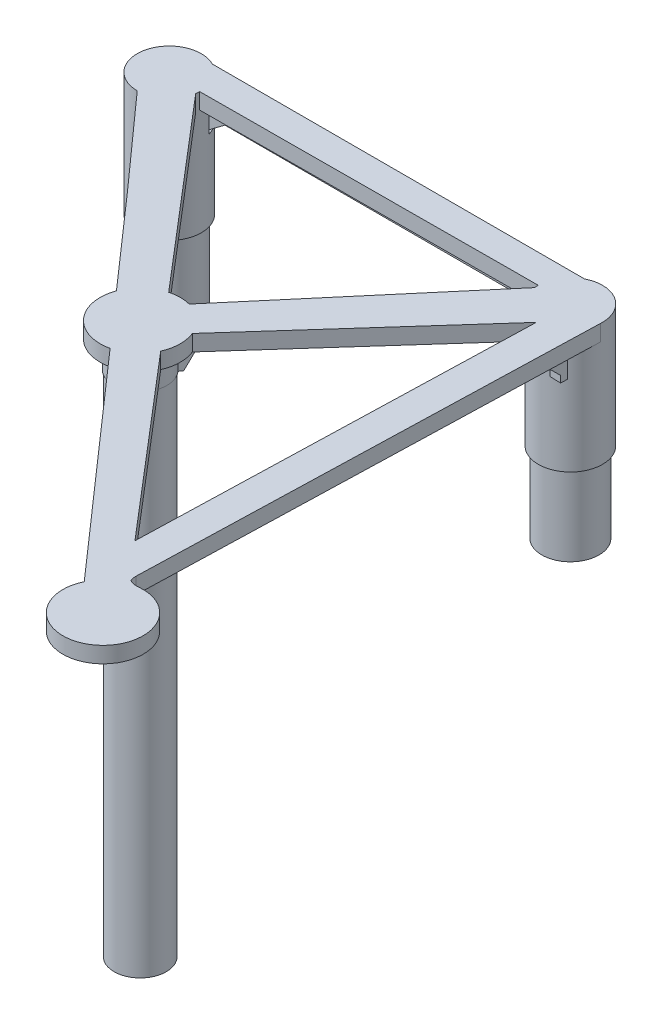
SolidWorks part; units mm, degrees
ref_plane "前视基准面" through (0, 0, 0) normal (0, 0, 1) x (1, 0, 0)
ref_plane "上视基准面" through (0, 0, 0) normal (0, 1, 0) x (1, 0, 0)
ref_plane "右视基准面" through (0, 0, 0) normal (1, 0, 0) x (0, 0, -1)
sketch "草图1" plane through (0, 0, 0) normal (0, 1, 0) x (1, 0, 0)
  line L1 (-18.6554, 0) -> (18.8446, -42.931)
  line L2 (18.8446, -42.931) -> (56.3446, 0)
  line L3 (-18.6554, 0) -> (56.3446, 0)
  dimension "D4" = 75
extrude "凸台-拉伸1" add sketch "草图1" along normal blind 3
sketch "草图2" plane through (0, 3, 0) normal (0, 1, 0) x (1, 0, 0)
  circle A0 centre (56.3446, 0) radius 5.35
  circle A1 centre (-18.6554, 0) radius 5.35
  dimension "D1" = 10.7
  dimension "D2" = 10.7
extrude "凸台-拉伸2" add sketch "草图2" against normal blind 23
sketch "草图3" plane through (0, 0, 0) normal (0, -1, 0) x (1, 0, 0)
  line L6 (8.6327, 17.5594) -> (1.1561, 9)
  line L7 (1.1561, 9) -> (33.7591, 9)
  line L8 (8.6327, 17.5594) -> (18.8446, 29.2503)
  line L9 (18.8446, 29.2503) -> (29.0566, 17.5594)
  line L10 (29.0566, 17.5594) -> (36.5332, 9)
  line L11 (36.5332, 9) -> (33.7591, 9)
  dimension "D4" = 26.8879
  dimension "D5" = 26.8879
  dimension "D6" = 35.3771
extrude "切除-拉伸1" cut sketch "草图3" against normal blind 3
sketch "草图4" plane through (0, 0, 0) normal (0, -1, 0) x (1, 0, 0)
  circle A0 centre (18.8446, 42.931) radius 5
  dimension "D1" = 10
extrude "凸台-拉伸3" add sketch "草图4" along normal blind 100
sketch "草图5" plane through (0, 0, 0) normal (0, 1, 0) x (1, 0, 0)
  circle A0 centre (18.8446, -42.931) radius 5
extrude "凸台-拉伸4" add sketch "草图5" along normal blind 3
sketch "草图6" plane through (0, -20, 0) normal (0, -1, 0) x (1, 0, 0)
  circle A0 centre (56.3446, 0) radius 5.35
extrude "凸台-拉伸5" add sketch "草图6" along normal blind 5
sketch "草图7" plane through (0, -20, 0) normal (0, -1, 0) x (1, 0, 0)
  circle A0 centre (-18.6554, 0) radius 5.35
extrude "凸台-拉伸6" add sketch "草图7" along normal blind 5
sketch "草图8" plane through (0, 3, 0) normal (0, 1, 0) x (1, 0, 0)
  line L0 (-18.6554, 5.35) -> (56.3446, 5.35)
  line L1 (56.3446, 5.35) -> (56.3446, -5.35)
  line L2 (56.3446, -5.35) -> (-18.6554, -5.35)
  line L3 (-18.6554, -5.35) -> (-18.6554, 5.35)
  arc A1 (52.8251, -4.0293) -> (50.9946, 0) centre (56.3446, 0) ccw construction
  arc A2 (-13.3054, 0) -> (-15.1358, -4.0293) centre (-18.6554, 0) ccw construction
  circle A3 centre (-18.6554, 0) radius 5.35 construction
extrude "凸台-拉伸7" add sketch "草图8" against normal blind 3
sketch "草图9" plane through (0, 3, 0) normal (0, 1, 0) x (1, 0, 0)
  line L0 (61.6946, 0) -> (18.8446, -47.931)
  line L1 (18.8446, -47.931) -> (-24.0054, 0)
  line L2 (-24.0054, 0) -> (61.6946, 0)
  arc A0 (56.3446, -5.35) -> (56.3446, 5.35) centre (56.3446, 0) ccw construction
  arc A1 (15.5553, -39.1653) -> (22.134, -39.1653) centre (18.8446, -42.931) ccw construction
  arc A2 (-18.6554, 5.35) -> (-18.6554, -5.35) centre (-18.6554, 0) ccw construction
extrude "凸台-拉伸8" add sketch "草图9" against normal blind 3
sketch "草图10" plane through (0, 0, 0) normal (0, -1, 0) x (1, 0, 0)
  line L0 (18.8446, 37.931) -> (-13.3137, 0.299)
  line L1 (-13.3137, 0.299) -> (50.9946, 0)
  line L2 (50.9946, 0) -> (18.8446, 37.931)
  arc A0 (13.8759, 42.373) -> (23.8134, 42.373) centre (18.8446, 42.931) ccw construction
  arc A1 (-18.6554, -5.35) -> (-19.2524, 5.3166) centre (-18.6554, 0) ccw construction
  circle A2 centre (56.3446, 0) radius 5.35 construction
  arc A3 (56.9416, 5.3166) -> (56.3446, -5.35) centre (56.3446, 0) ccw construction
extrude "切除-拉伸2" cut sketch "草图10" against normal blind 3
sketch "草图12" plane through (0, 3, 0) normal (0, 1, 0) x (1, 0, 0)
  circle A0 centre (-18.6554, 0) radius 6
  circle A1 centre (56.3446, 0) radius 6
  dimension "D1" = 12
  dimension "D2" = 12
extrude "凸台-拉伸10" add sketch "草图12" against normal blind 13
sketch "草图13" plane through (0, -25, 0) normal (0, -1, 0) x (1, 0, 0)
  circle A0 centre (-18.6554, 0) radius 3
  circle A1 centre (56.3446, 0) radius 3
  dimension "D1" = 6
  dimension "D2" = 6
extrude "切除-拉伸3" cut sketch "草图13" against normal blind 23
sketch "草图14" plane through (0, -100, 0) normal (0, -1, 0) x (1, 0, 0)
  circle A0 centre (18.8446, 42.931) radius 3.125
  dimension "D1" = 6.25
extrude "切除-拉伸5" cut sketch "草图14" against normal blind 100
sketch "草图15" plane through (0, -10, 0) normal (0, -1, 0) x (1, 0, 0)
  circle A0 centre (56.3446, 0) radius 5.35
  circle A1 centre (56.3446, 0) radius 6
extrude "凸台-拉伸11" add sketch "草图15" along normal blind 5
sketch "草图16" plane through (0, -10, 0) normal (0, -1, 0) x (1, 0, 0)
  circle A0 centre (-18.6554, 0) radius 3
  circle A1 centre (-18.6554, 0) radius 6
extrude "凸台-拉伸12" add sketch "草图16" along normal blind 5
sketch "草图17" plane through (0, -25, 0) normal (0, -1, 0) x (1, 0, 0)
  circle A0 centre (-18.6554, 0) radius 3
  circle A1 centre (-18.6554, 0) radius 5.35
extrude "凸台-拉伸13" add sketch "草图17" along normal blind 5
sketch "草图18" plane through (0, -25, 0) normal (0, -1, 0) x (1, 0, 0)
  circle A0 centre (56.3446, 0) radius 3
  circle A1 centre (56.3446, 0) radius 5.35
extrude "凸台-拉伸14" add sketch "草图18" along normal blind 5
sketch "草图20" plane through (0, -15, 0) normal (0, -1, 0) x (1, 0, 0)
  circle A0 centre (-18.6554, 0) radius 5.35
  circle A1 centre (-18.6554, 0) radius 6
extrude "凸台-拉伸15" add sketch "草图20" along normal blind 5
sketch "草图21" plane through (0, -15, 0) normal (0, -1, 0) x (1, 0, 0)
  circle A0 centre (56.3446, 0) radius 5.35
  circle A1 centre (56.3446, 0) radius 6
extrude "凸台-拉伸16" add sketch "草图21" along normal blind 5
sketch "草图22" plane through (0, -30, 0) normal (0, -1, 0) x (1, 0, 0)
  circle A0 centre (-18.6554, 0) radius 3
  circle A1 centre (-18.6554, 0) radius 5.35
extrude "凸台-拉伸17" add sketch "草图22" along normal blind 5
sketch "草图23" plane through (0, -30, 0) normal (0, -1, 0) x (1, 0, 0)
  circle A0 centre (56.3446, 0) radius 3
  circle A1 centre (56.3446, 0) radius 5.35
extrude "凸台-拉伸18" add sketch "草图23" along normal blind 5
sketch "草图25" plane through (0, 3, 0) normal (0, 1, 0) x (1, 0, 0)
  circle A0 centre (18.8446, -42.931) radius 7.5
  dimension "D1" = 15
extrude "凸台-拉伸20" add sketch "草图25" against normal blind 3
sketch "草图28" plane through (0, 3, 0) normal (0, 1, 0) x (1, 0, 0)
  line L1 (-3.3796, -23.0714) -> (2.0936, -18.3287)
  line L2 (-3.3796, -23.0714) -> (64.3216, -100.0268)
  line L3 (64.3216, -100.0268) -> (66.8686, -97.9101)
  line L4 (-18.6414, -6) -> (11.8821, -40.1429) construction
  line L5 (2.0936, -18.3287) -> (68.6526, -96.2167)
  line L6 (16.9224, -35.6815) -> (-12.7353, -0.9759) construction
  line L7 (68.6526, -96.2167) -> (66.8686, -97.9101)
extrude "凸台-拉伸21" add sketch "草图28" against normal blind 3
sketch "草图29" plane through (0, 3, 0) normal (0, 1, 0) x (1, 0, 0)
  line L0 (56.3446, 0) -> (53.7411, -88)
  line L1 (20.5226, -50.2409) -> (64.3216, -100.0268) construction
  line L2 (53.7411, -88) -> (59.7411, -88)
  line L3 (56.3446, 0) -> (62.3446, 0)
  line L4 (62.3446, 0) -> (59.7411, -88)
  arc A1 (56.3307, -6) -> (53.6285, 5.35) centre (56.3446, 0) ccw construction
  dimension "D2" = 6
  dimension "D3" = 88
extrude "凸台-拉伸23" add sketch "草图29" against normal blind 3
sketch "草图30" plane through (0, 3, 0) normal (0, 1, 0) x (1, 0, 0)
  circle A0 centre (62.6532, -93.6946) radius 7.5
  dimension "D1" = 15
extrude "凸台-拉伸24" add sketch "草图30" against normal blind 3
fillet "圆角1" radius 3 2 edges at (60.3876, 1.5, 86.545) (59.8043, 1.5, 85.8624)
sketch "草图31" plane through (0, 0, 0) normal (0, -1, 0) x (1, 0, 0)
  line L0 (-14.7236, -1.6282) -> (-14.7236, -3.6282)
  line L1 (-14.7236, -3.6282) -> (53.5274, -3.6282)
  line L2 (53.5274, -3.6282) -> (53.8249, -1.6282)
  line L3 (53.8249, -1.6282) -> (-14.7236, -1.6282)
  line L4 (49.6098, 80.1025) -> (51.1303, 78.8032)
  line L5 (22.3188, 45.0877) -> (51.1303, 78.8032)
  line L6 (49.6098, 80.1025) -> (20.7983, 46.387)
  line L7 (-15.3496, 4.0864) -> (-13.8291, 2.7871)
  line L8 (20.3259, 39.1868) -> (51.8689, 1.9719)
  line L9 (20.3259, 39.1868) -> (21.8516, 40.4799)
  line L10 (51.8689, 1.9719) -> (53.3946, 3.265)
  line L11 (21.8516, 40.4799) -> (53.3946, 3.265)
  line L12 (20.7983, 46.387) -> (22.3188, 45.0877)
  line L13 (15.5768, 40.2768) -> (17.0973, 38.9775)
  line L14 (17.0973, 38.9775) -> (-13.8291, 2.7871)
  line L15 (-15.3496, 4.0864) -> (15.5768, 40.2768)
  line L16 (56.0939, 78.8643) -> (58.3189, 3.6596)
  line L17 (58.3189, 3.6596) -> (60.3198, 3.6596)
  line L18 (60.3198, 3.6596) -> (58.093, 78.9234)
  line L19 (58.093, 78.9234) -> (56.0939, 78.8643)
  circle A0 centre (-18.6554, 0) radius 5.35 construction
  circle A1 centre (56.3446, 0) radius 3 construction
  dimension "D1" = 2
  dimension "D2" = 2
  dimension "D3" = 2
  dimension "D4" = 2
  dimension "D5" = 2
extrude "凸台-拉伸29" add sketch "草图31" along normal blind 5
sketch "草图35" plane through (0, 0, -3.6282) normal (0, 0, -1) x (-1, 0, 0)
  line L0 (13.8766, -5) -> (9.8766, -2)
  line L1 (9.8766, -2) -> (-47.5659, -2)
  line L2 (-47.5659, -2) -> (-51.5659, -5)
  line L3 (-51.5659, -5) -> (13.8766, -5)
  line L4 (13.8766, 0) -> (-51.5659, 0) construction
  dimension "D1" = 2
  dimension "D2" = 4
  dimension "D3" = 4
sketch "草图36" plane through (0, -5, 0) normal (0, -1, 0) x (1, 0, 0)
  line L0 (18.8446, -3.6282) -> (18.8446, -1.6282)
  line L1 (-9.8766, -3.6282) -> (47.5659, -3.6282) construction
  line L2 (50.5698, -1.6282) -> (-12.8805, -1.6282) construction
sweep "切除-扫描1" cut profiles "草图35" path "草图36"
sketch "草图37" plane through (60.3752, 0, 1.7863) normal (0.9996, 0, 0.0296) x (0.0296, 0, -0.9996)
  line L0 (-2.7315, -5) -> (-6.7315, -1)
  line L1 (-6.7315, -1) -> (-73.1709, -1)
  line L2 (-73.1709, -1) -> (-77.1709, -5)
  line L3 (-77.1709, -5) -> (-2.7315, -5)
  line L5 (-82.8983, 0) -> (1.4889, 0) construction
  dimension "D1" = 1
  dimension "D2" = 4
  dimension "D3" = 4
sketch "草图38" plane through (0, -5, 0) normal (0, -1, 0) x (1, 0, 0)
  line L0 (59.1937, 41.72) -> (57.1928, 41.72)
  line L1 (60.1761, 8.5148) -> (58.2113, 74.9252) construction
  line L2 (56.0939, 78.8643) -> (58.2589, 5.6864) construction
sweep "切除-扫描3" cut profiles "草图37" path "草图38"
sketch "草图39" plane through (58.3761, 0, 1.7271) normal (0.9996, 0, 0.0296) x (0.0296, 0, -0.9996)
  line L0 (-3.961, -3.8296) -> (-3.961, -5)
  line L1 (-3.961, -5) -> (-2.7315, -5)
  line L2 (-3.961, -3.8296) -> (-3.961, -3.2722)
  line L3 (-3.961, -3.2722) -> (-2.7315, -4.5017)
  line L4 (-2.7315, 0) -> (-2.7315, -5) construction
  line L5 (-2.7315, -4.5017) -> (-2.7315, -5)
extrude "凸台-拉伸31" add sketch "草图39" along normal blind 2
sketch "草图40" plane through (-10.8895, 0, 9.3056) normal (-0.7602, 0, 0.6497) x (0.6497, 0, 0.7602)
  line L0 (-5.1212, -5) -> (-3.1212, -1)
  line L2 (39.938, -5) -> (-6.1212, -5) construction
  line L3 (-3.1212, -1) -> (36.938, -1)
  line L5 (36.938, -1) -> (38.938, -5)
  line L6 (38.938, -5) -> (-5.1212, -5)
  line L7 (39.938, 0) -> (-6.1212, 0) construction
  dimension "D1" = 1
  dimension "D2" = 2
  dimension "D3" = 1
  dimension "D4" = 1
  dimension "D5" = 2
sketch "草图42" plane through (0, -5, 0) normal (0, -1, 0) x (1, 0, 0)
  line L0 (0.0951, 22.1599) -> (1.5521, 20.7864)
  line L1 (-12.9172, 6.9328) -> (13.1074, 37.387) construction
  line L2 (-13.5363, 3.1298) -> (16.6406, 38.443) construction
sweep "切除-扫描5" cut profiles "草图40" path "草图42"
sketch "草图43" plane through (31.1568, 0, 26.4083) normal (-0.7628, 0, -0.6466) x (-0.6466, 0, 0.7628)
  line L0 (14.7346, -5) -> (12.7346, -1)
  line L1 (15.7346, -5) -> (-30.8257, -5) construction
  line L2 (12.7346, -1) -> (-27.8257, -1)
  line L3 (-27.8257, -1) -> (-29.8257, -5)
  line L4 (14.7346, -5) -> (-29.8257, -5)
  line L5 (15.7346, 0) -> (-30.8257, 0) construction
  dimension "D1" = 1
  dimension "D2" = 1
  dimension "D3" = 1
  dimension "D4" = 2
  dimension "D5" = 2
sketch "草图44" plane through (0, -5, 0) normal (0, -1, 0) x (1, 0, 0)
  line L0 (36.0357, 20.6522) -> (37.4729, 22.0498)
  line L1 (22.9229, 36.1228) -> (49.1484, 5.1816) construction
  line L2 (52.36, 4.4858) -> (22.5858, 39.6138) construction
sweep "切除-扫描6" cut profiles "草图43" path "草图44"
sketch "草图46" plane through (-10.8895, 0, 9.3056) normal (-0.7602, 0, 0.6497) x (0.6497, 0, 0.7602)
  line L0 (50.8218, -5) -> (52.8218, -1)
  line L1 (93.1256, -5) -> (49.8218, -5) construction
  line L2 (52.8218, -1) -> (88.1256, -1)
  line L3 (88.1256, -1) -> (93.1256, 0)
  line L4 (93.1256, 0) -> (93.1256, -5)
  line L5 (93.1256, -5) -> (50.8218, -5)
  line L6 (93.1256, 0) -> (49.8218, 0) construction
  dimension "D1" = 1
  dimension "D2" = 1
  dimension "D3" = 2
  dimension "D4" = 5
sketch "草图47" plane through (0, -5, 0) normal (0, -1, 0) x (1, 0, 0)
  line L0 (37.0322, 62.3055) -> (35.5118, 63.6048)
  line L1 (22.9341, 45.8078) -> (51.1303, 78.8032) construction
  line L2 (23.4264, 49.4624) -> (46.3616, 76.3014) construction
sweep "切除-扫描7" cut profiles "草图46" path "草图47"
sketch "草图48" plane through (60.3752, 0, 1.7863) normal (0.9996, 0, 0.0296) x (0.0296, 0, -0.9996)
  line L0 (-73.1709, -1) -> (-77.1709, 0)
  line L1 (-77.1709, 0) -> (-77.1709, -5)
  line L2 (-73.1709, -1) -> (-77.1709, -5)
sketch "草图49" plane through (0, -1, 0) normal (0, -1, 0) x (1, 0, 0)
  line L0 (58.2113, 74.9252) -> (56.2104, 74.9252)
  line L1 (56.2104, 74.9252) -> (55.38, 74.9252)
sweep "切除-扫描8" cut profiles "草图48" path "草图49"
sketch "草图50" plane through (0, 3, 0) normal (0, 1, 0) x (1, 0, 0)
  circle A0 centre (18.8446, -42.931) radius 5
  dimension "D1" = 10
extrude "凸台-拉伸32" add sketch "草图50" against normal blind 103
sketch "草图51" plane through (0, -100, 0) normal (0, -1, 0) x (1, 0, 0)
  circle A0 centre (18.8446, 42.931) radius 5
  circle A1 centre (18.8446, 42.931) radius 4.875
  dimension "D1" = 9.75
extrude "切除-拉伸6" cut sketch "草图51" against normal blind 95
sketch "草图52" plane through (0, -100, 0) normal (0, -1, 0) x (1, 0, 0)
  line L5 (21.6731, 45.7594) -> (16.0162, 45.7594)
  line L6 (21.6731, 45.7594) -> (21.6731, 40.1026)
  line L7 (21.6731, 40.1026) -> (16.0162, 40.1026)
  line L11 (16.0162, 45.7594) -> (16.0162, 40.1026)
  arc A1 (22.5858, 39.6138) -> (22.9341, 45.8078) centre (18.8446, 42.931) ccw construction
extrude "切除-拉伸7" cut sketch "草图52" against normal blind 100
